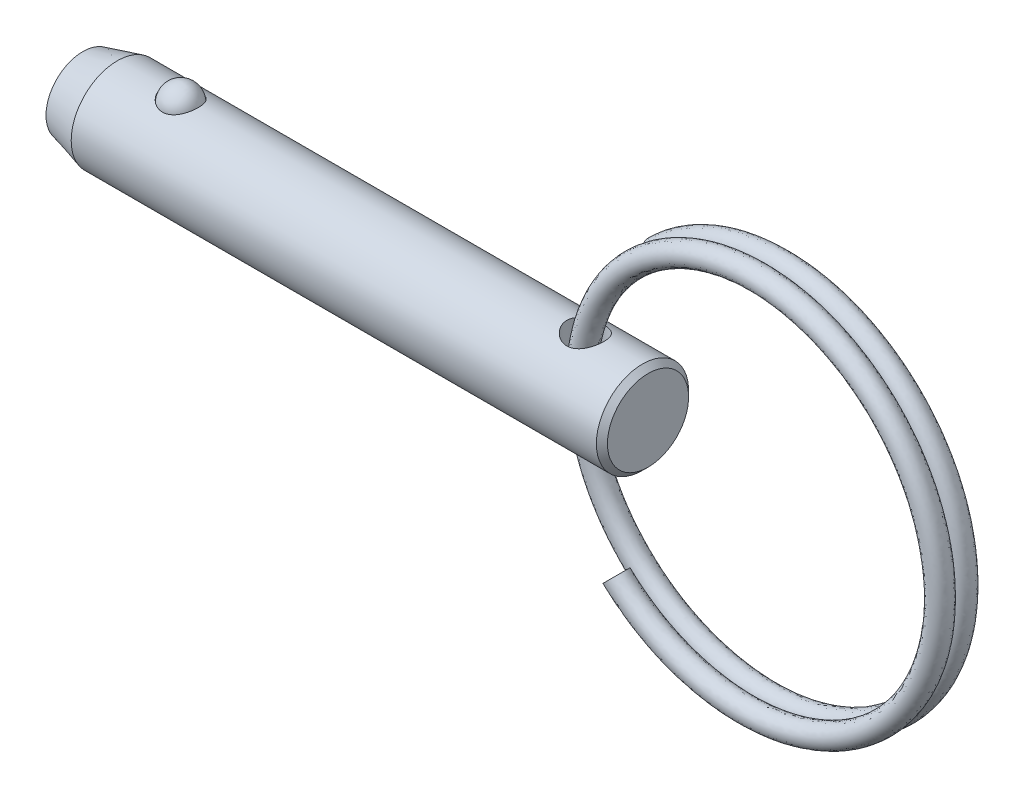
SolidWorks part; units mm, degrees
material "AISI 304"
ref_plane "Front" through (0, 0, 0) normal (0, 0, 1) x (1, 0, 0)
ref_plane "Top" through (0, 0, 0) normal (0, 1, 0) x (1, 0, 0)
ref_plane "Right" through (0, 0, 0) normal (1, 0, 0) x (0, 0, -1)
sketch "Sketch1" plane through (0, 0, 0) normal (0, 0, 1) x (1, 0, 0)
  line L0 (5.588, 2.794) -> (5.207, 3.175)
  line L1 (5.207, 3.175) -> (5.588, 3.175) construction
  line L4 (5.588, 2.794) -> (5.588, 0)
  line L5 (5.588, 3.175) -> (5.588, 2.794) construction
  line L16 (5.207, 3.175) -> (-30.9549, 3.175)
  line L17 (-33.3248, 3.175) -> (-33.3248, 2.54) construction
  line L19 (-30.9549, 3.175) -> (-33.3248, 3.175) construction
  line L22 (-33.3248, -3.175) -> (-30.9549, -3.175) construction
  line L23 (-26.5903, 2.8575) -> (-26.5903, -2.8575) construction
  line L24 (-33.3248, 0) -> (5.588, 0)
  line L27 (5.588, 0) -> (8.382, 0) construction
  line L29 (-33.3248, 0) -> (-33.3248, -2.54) construction
  line L36 (0, 0) -> (0, 3.175) construction
  line L37 (-33.3248, 2.54) -> (-33.3248, 0)
  line L38 (-30.9549, -3.175) -> (5.588, -3.175) construction
  line L39 (-33.3248, -2.54) -> (-33.3248, -3.175) construction
  line L40 (-30.9549, 3.175) -> (-33.3248, 2.54)
  line L42 (-30.9549, -3.175) -> (-33.3248, -2.54) construction
  line L43 (-30.9549, 3.175) -> (-30.9549, -3.175) construction
  circle A2 centre (-26.5903, 2.8575) radius 1.2319 construction
  point P35 (-25.4, 3.175)
  dimension "D2" = 5.715
  dimension "D11" = 0.9144
  dimension "A" = 6.35
  dimension "D" = 5.588
  dimension "E" = 7.2644
  dimension "D3" = 0.381
  dimension "Useable Length" = 25.4
  dimension "D12" = 5.08
  dimension "C" = 7.9248
  dimension "A1" = 15
revolve "Revolve1" add sketch "Sketch1" angle 360 about L27
sketch "Sketch2" plane through (0, 0, 0) normal (0, 0, 1) x (1, 0, 0)
  line L0 (-25.333, 2.8575) -> (-27.8476, 2.8575)
  line L1 (-26.5903, 4.0894) -> (-26.5903, 4.1148) construction
  line L2 (-25.333, 2.8575) -> (-22.8184, 2.8575) construction
  circle A0 centre (-26.5903, 2.8575) radius 1.2319 construction
  circle A1 centre (-26.5903, 2.8575) radius 1.2319 construction
  arc A2 (-27.8476, 2.8575) -> (-25.333, 2.8575) centre (-26.5903, 2.8575) cw
  dimension "D1" = 0.0254
revolve "Cut-Revolve1" cut sketch "Sketch2" angle 360 about L2
sketch "Sketch3" plane through (0, 0, 0) normal (0, 0, 1) x (1, 0, 0)
  line L0 (-25.3584, 2.8575) -> (-27.8222, 2.8575)
  line L1 (-25.3584, 2.8575) -> (-22.8946, 2.8575) construction
  circle A0 centre (-26.5903, 2.8575) radius 1.2319 construction
  arc A1 (-25.3584, 2.8575) -> (-27.8222, 2.8575) centre (-26.5903, 2.8575) ccw
revolve "Revolve2" add sketch "Sketch3" angle 360 about L1
sketch "Sketch4" plane through (0, 0, 0) normal (0, 0, 1) x (1, 0, 0)
  line L1 (1.27, -3.175) -> (2.54, -3.175)
  line L2 (1.27, -3.175) -> (1.27, 3.175)
  line L3 (1.27, 3.175) -> (2.54, 3.175)
  line L4 (2.54, -3.175) -> (2.54, 3.175)
  line L5 (1.27, -3.175) -> (1.27, -4.445) construction
  line L6 (2.54, 3.175) -> (5.588, 3.175) construction
  line L8 (0, -3.175) -> (0, 3.175) construction
  line L9 (0, 0) -> (1.27, 0) construction
  line L11 (1.27, 0) -> (2.54, 0) construction
  line L12 (5.207, 3.175) -> (-30.9549, 3.175) construction
  line L14 (-30.9549, -3.175) -> (5.588, -3.175) construction
  dimension "D1" = 2.54
revolve "Cut-Revolve2" cut sketch "Sketch4" angle 360 about L2
sketch "Sketch5" plane through (0, 0, 0) normal (0, 0, 1) x (1, 0, 0)
  line L0 (0, 0) -> (0.293, 0) construction
  line L1 (0.293, 0) -> (0.293, 3.175) construction
  line L2 (5.207, 3.175) -> (-30.9549, 3.175) construction
  line L3 (13.755, 0) -> (27.217, 0) construction
  line L4 (2.54, 3.175) -> (2.247, 3.175) construction
  line L5 (1.27, 3.175) -> (2.54, 3.175) construction
  line L6 (0.6728, 3.175) -> (0.6728, -3.175) construction
  line L7 (0.293, 3.175) -> (0, 3.175) construction
  line L8 (1.27, -3.175) -> (2.54, -3.175) construction
  line L9 (0.6728, -3.175) -> (2.54, -3.175) construction
  line L10 (0.293, 0) -> (13.755, 0) construction
  line L11 (13.755, 0) -> (8.7098, -10.8195) construction
  line L12 (2.247, 3.175) -> (0.6728, 3.175) construction
  line L13 (13.755, 11.938) -> (13.755, 13.462) construction
  line L14 (8.7098, -10.8195) -> (8.3878, -11.5101) construction
  circle A0 centre (13.755, 0) radius 13.462
  circle A1 centre (13.755, 0) radius 11.938 construction
  circle A2 centre (13.755, 0) radius 12.7 construction
  point P26 (13.755, 12.7)
  dimension "D1" = 65
  dimension "R Ring Dia" = 25.4
  dimension "Ring OD" = 1.524
curve "Helix/Spiral1" pitch 1.5494 height 1.3557 radius 13.462 left hand yes centre (13.755, 0, 0) axis (0, 0, -1) start towards (1, 0, 0)
sketch "Sketch6" plane through (114.0038, 0, 0) normal (0, 1, 0) x (0, 0, -1)
  line L0 (0, 112.1868) -> (0, 112.9488) construction
  line L1 (0, 112.9488) -> (0, 113.7108) construction
  circle A0 centre (0, 112.9488) radius 0.762
  dimension "D1" = 1.524
sketch "Sketch7" plane through (0, 0, 0) normal (0, 0, 1) x (1, 0, 0)
  circle A0 centre (13.755, 0) radius 13.462 construction
  circle A1 centre (13.755, 0) radius 13.462
curve "Helix/Spiral2" pitch 1.5494 height 1.3557 radius 13.462 left hand yes centre (13.755, 0, 0) axis (0, 0, 1) start towards (1, 0, 0)
sweep "Sweep1" add profiles "Sketch6" path "Helix/Spiral1"
sweep "Sweep2" add profiles "Sketch6<2>" path "Helix/Spiral2"
sketch "Sketch6<2>" plane through (114.0038, 0, 0) normal (0, 1, 0) x (0, 0, -1) same geometry as "Sketch6"
ref_plane "Plane1" through (0, -10.8195, 0) normal (0, 1, 0) x (-1, 0, 0)
sketch "Sketch8" plane through (0, -10.8195, 0) normal (0, 1, 0) x (-1, 0, 0)
  line L0 (143.6902, 0) -> (-8.7098, 0) construction
  line L1 (10.3402, -0.7779) -> (4.5066, -0.7779)
  line L2 (3.5004, -0.9415) -> (-7.2005, -4.517)
  line L3 (-7.2005, 4.517) -> (3.5004, 0.9415)
  line L4 (4.5066, 0.7779) -> (130.4738, 0.7779)
  line L5 (131.48, 0.9415) -> (142.1809, 4.517)
  line L6 (124.6402, -0.7779) -> (130.4738, -0.7779)
  line L7 (131.48, -0.9415) -> (142.1809, -4.517)
  line L8 (10.3402, -0.7779) -> (10.3402, 0.7779) construction
  arc A0 (-7.2005, 4.517) -> (-7.2005, -4.517) centre (-8.7098, 0) ccw
  arc A1 (142.1809, -4.517) -> (142.1809, 4.517) centre (143.6902, 0) ccw
  arc A2 (4.5066, -0.7779) -> (3.5004, -0.9415) centre (4.5066, -3.9529) ccw
  arc A3 (3.5004, 0.9415) -> (4.5066, 0.7779) centre (4.5066, 3.9529) ccw
  arc A4 (130.4738, -0.7779) -> (131.48, -0.9415) centre (130.4738, -3.9529) cw
  arc A5 (130.4738, 0.7779) -> (131.48, 0.9415) centre (130.4738, 3.9529) ccw
  point P6 (10.3402, 0)
  point P16 (3.9902, -0.7779)
  point P20 (3.9902, 0.7779)
  point P23 (130.9902, -0.7779)
  point P26 (130.9902, 0.7779)
  dimension "D2" = 4.7625
  dimension "D3" = 1.5557
  dimension "D6" = 3.175
  dimension "Lanyard Length" = 152.4
  dimension "D4" = 6.35
  dimension "D5" = 12.7
ref_plane "Plane2" through (-10.3402, 0, 0) normal (1, 0, 0) x (0, 0, -1)
sketch "Sketch9" plane through (-10.3402, 0, 0) normal (1, 0, 0) x (0, 0, -1)
  circle A0 centre (0.7779, -10.8195) radius 0.7779
sweep "Sweep3" [suppressed] add profiles "Sketch9" path "Sketch8"
sketch "Sketch10" [suppressed] plane through (-10.3402, 0, 0) normal (1, 0, 0) x (0, 0, -1)
  arc A0 (-0.3849, -10.1482) -> (-0.3849, -11.4908) centre (-0.7779, -10.8195) ccw
  circle A1 centre (0.7779, -10.8195) radius 0.7779
  arc A2 (0.3849, -11.4908) -> (0.3849, -10.1482) centre (0.7779, -10.8195) ccw
  arc A3 (-0.3849, -11.4908) -> (0.3849, -11.4908) centre (0, -12.1485) cw
  arc A4 (-0.3869, -9.3301) -> (-0.3869, -12.3089) centre (-0.7779, -10.8195) ccw
  arc A5 (0.3869, -12.3089) -> (0.3869, -9.3301) centre (0.7779, -10.8195) ccw
  circle A6 centre (-0.7779, -10.8195) radius 1.5399 construction
  circle A7 centre (-0.7779, -10.8195) radius 0.7779 construction
  arc A8 (-0.3849, -10.1482) -> (0.3849, -10.1482) centre (0, -9.4905) ccw
  arc A9 (-0.3869, -9.3301) -> (0.3869, -9.3301) centre (0, -7.856) ccw
  arc A10 (0.3869, -12.3089) -> (-0.3869, -12.3089) centre (0, -13.783) ccw
  point P4 (-0.034, -10.2746)
  point P8 (2.3178, -10.502)
  point P9 (0.762, -10.502)
  dimension "D3" = 1.524
  dimension "D4" = 0.762
  dimension "D2" = 0.762
  dimension "D1" = 0
extrude "Extrude1" [suppressed] add sketch "Sketch10" along normal blind 5.715 separate body
sketch "Sketch11" [suppressed] plane through (-124.6402, 0, 0) normal (1, 0, 0) x (0, 0, -1)
  arc A4 (-0.3849, -10.1482) -> (-0.3849, -11.4908) centre (-0.7779, -10.8195) ccw
  arc A5 (0.3849, -11.4908) -> (-0.3849, -11.4908) centre (0, -12.1485) ccw
  arc A6 (0.3849, -11.4908) -> (0.3849, -10.1482) centre (0.7779, -10.8195) ccw
  arc A7 (-0.3849, -10.1482) -> (0.3849, -10.1482) centre (0, -9.4905) ccw
  arc A8 (-0.3849, -10.1482) -> (-0.3849, -11.4908) centre (-0.7779, -10.8195) ccw
  arc A9 (0.3849, -11.4908) -> (-0.3849, -11.4908) centre (0, -12.1485) ccw
  arc A10 (0.3849, -11.4908) -> (0.3849, -10.1482) centre (0.7779, -10.8195) ccw
  arc A11 (-0.3849, -10.1482) -> (0.3849, -10.1482) centre (0, -9.4905) ccw
  arc A12 (-0.3869, -9.3301) -> (-0.3869, -12.3089) centre (-0.7779, -10.8195) ccw
  arc A13 (0.3869, -12.3089) -> (-0.3869, -12.3089) centre (0, -13.783) ccw
  arc A14 (0.3869, -12.3089) -> (0.3869, -9.3301) centre (0.7779, -10.8195) ccw
  arc A15 (-0.3869, -9.3301) -> (0.3869, -9.3301) centre (0, -7.856) ccw
  arc A16 (-0.3869, -9.3301) -> (-0.3869, -12.3089) centre (-0.7779, -10.8195) ccw
  arc A17 (0.3869, -12.3089) -> (-0.3869, -12.3089) centre (0, -13.783) ccw
  arc A18 (0.3869, -12.3089) -> (0.3869, -9.3301) centre (0.7779, -10.8195) ccw
  arc A19 (-0.3869, -9.3301) -> (0.3869, -9.3301) centre (0, -7.856) ccw
  dimension "D1" = 0
  dimension "D2" = 0
extrude "Extrude2" [suppressed] add sketch "Sketch11" against normal blind 5.715 separate body
sketch "Sketch12" plane through (0, -10.8195, 0) normal (0, 1, 0) x (-1, 0, 0)
  line L0 (174.4712, -5.2864) -> (168.9086, -5.2864) construction
  line L1 (174.4712, -5.9214) -> (158.1026, -5.9214)
  line L2 (174.4712, -5.9214) -> (174.4712, -4.6514)
  line L3 (174.4712, -4.6514) -> (158.3265, -4.6514)
  line L4 (158.1026, -5.9214) -> (158.3265, -4.6514) construction
  line L5 (158.1026, -5.9214) -> (142.7212, -0.3231)
  line L6 (168.9086, -5.2864) -> (158.2146, -5.2864) construction
  line L7 (158.3265, -4.6514) -> (143.1555, 0.8704)
  line L8 (142.7212, -0.3231) -> (143.1555, 0.8704)
  line L9 (158.2146, -5.2864) -> (148.1655, -1.6289) construction
  line L10 (148.1655, -1.6289) -> (142.9383, 0.2737) construction
  arc A0 (142.1809, -4.517) -> (142.1809, 4.517) centre (143.6902, 0) ccw construction
  dimension "D1" = 20
  dimension "D2" = 31.75
  dimension "D3" = 1.27
  dimension "D4" = 5.5626
extrude "Extrude3" [suppressed] add sketch "Sketch12" along normal mid plane 12.7 separate body
sketch "Sketch13" [suppressed] plane through (0, 0, -4.6514) normal (0, 0, 1) x (1, 0, 0)
  line L0 (-174.4712, -10.8195) -> (-158.3265, -10.8195) construction
  line L1 (-172.4782, -4.4695) -> (-174.4712, -4.4695)
  line L2 (-174.4712, -4.4695) -> (-158.3265, -4.4695) construction
  line L3 (-174.4712, -4.4695) -> (-176.4642, -4.4695)
  line L4 (-176.4642, -4.4695) -> (-176.4642, -17.1695)
  line L5 (-176.4642, -17.1695) -> (-174.4712, -17.1695)
  line L6 (-174.4712, -17.1695) -> (-172.4782, -17.1695)
  line L7 (-174.4712, -17.1695) -> (-158.3265, -17.1695) construction
  arc A0 (-172.4782, -4.4695) -> (-172.4782, -17.1695) centre (-163.3587, -10.8195) ccw
  circle A1 centre (-168.9086, -10.8195) radius 2.5781
  dimension "D1" = 5.1562
  dimension "D2" = 11.1125
extrude "Extrude4" [suppressed] cut sketch "Sketch13" against normal up to surface (1.27 mm away)
sketch "Sketch14" [suppressed] plane through (-17.0257, 0, 46.7778) normal (-0.342, 0, 0.9397) x (0.9397, 0, 0.342)
  line L3 (-136.2175, -4.4695) -> (-134.2245, -4.4695)
  line L4 (-134.2245, -4.4695) -> (-132.2315, -4.4695)
  line L5 (-132.2315, -4.4695) -> (-132.2315, -17.1695)
  line L6 (-132.2315, -17.1695) -> (-134.2245, -17.1695)
  line L7 (-134.2245, -17.1695) -> (-136.2175, -17.1695)
  line L8 (-134.2245, -4.4695) -> (-134.2245, -17.1695) construction
  line L9 (-150.3692, -4.4695) -> (-134.2245, -4.4695) construction
  line L10 (-150.4811, -10.8195) -> (-139.7871, -10.8195) construction
  arc A0 (-136.2175, -17.1695) -> (-136.2175, -4.4695) centre (-145.337, -10.8195) ccw
  circle A1 centre (-139.7871, -10.8195) radius 2.5781
  dimension "D1" = 5.1562
  dimension "D2" = 11.1125
extrude "Extrude6" [suppressed] cut sketch "Sketch14" against normal up to surface (1.27 mm away)
sketch "Sketch15" [suppressed] plane through (0, 0, 0) normal (0, 0, 1) x (1, 0, 0)
  line L1 (-258.031, -4.4695) -> (-99.281, -4.4695)
  line L2 (-258.031, -4.4695) -> (-270.731, -17.1695)
  line L3 (-270.731, -17.1695) -> (-111.981, -17.1695)
  line L4 (-99.281, -4.4695) -> (-111.981, -17.1695)
  line L5 (-325.1006, -4.4695) -> (-310.949, -4.4695) construction
  line L6 (-325.1006, -17.1695) -> (-310.949, -17.1695) construction
  circle A0 centre (-321.531, -10.8195) radius 2.5781 construction
  dimension "D1" = 63.5
  dimension "D2" = 158.75
  dimension "D3" = 45
extrude "Extrude7" [suppressed] cut sketch "Sketch15" against normal through all and the other way through all
move or copy body "Body-Move/Copy1" [suppressed] bodies to move or copy 147 151 144 copy no translate (152.4, 0, 0)
sketch "Sketch16" [suppressed] plane through (0, 0, 0) normal (0, 0, 1) x (1, 0, 0)
  line L0 (-111.981, -6.057) -> (-111.981, -9.232) construction
  line L1 (-111.981, -9.232) -> (-109.441, -8.2795) construction
  line L2 (-109.441, -8.2795) -> (-114.521, -13.3595) construction
  line L3 (-114.521, -13.3595) -> (-111.981, -12.407) construction
  line L4 (-111.981, -12.407) -> (-111.981, -15.582) construction
  line L5 (-112.7589, -11.5974) -> (-111.2032, -10.0416) construction
  line L6 (-105.631, -15.582) -> (-105.631, -12.407) construction
  line L7 (-105.631, -12.407) -> (-108.171, -13.3595) construction
  line L8 (-108.171, -13.3595) -> (-103.091, -8.2795) construction
  line L9 (-103.091, -8.2795) -> (-105.631, -9.232) construction
  line L10 (-105.631, -9.232) -> (-105.631, -6.057) construction
  line L11 (-104.8532, -10.0416) -> (-106.4089, -11.5974) construction
  line L14 (-4.7291, -10.8195) -> (-283.0963, -10.8195) construction
  dimension "D1" = 3.175
  dimension "D2" = 3.175
  dimension "D3" = 5.08
  dimension "D4" = 1.5875
equation "\"D12@Sketch1\"=\"A@Sketch1\" * 0.80"
equation "\"D2@Sketch1\"=\"A@Sketch1\" * 0.9"
equation "\"D1@Sketch4\" = \"A@Sketch1\" / 2.5"
equation "\"Ring OD@Sketch5\" = \"R Ring Dia@Sketch5\" * 0.06"
equation "\"D4@Helix/Spiral1\"=\"Ring OD@Sketch5\" + 0.001"
equation "\"D1@Sketch6\"=\"Ring OD@Sketch5\""
equation "\"D4@Helix/Spiral2\" = \"D4@Helix/Spiral1\""
equation "\"D5@Helix/Spiral2\" = \"D5@Helix/Spiral1\""
equation "\"D1@Sketch14\" = \"D1@Sketch13\""
equation "\"D2@Sketch14\" = \"D2@Sketch13\""
